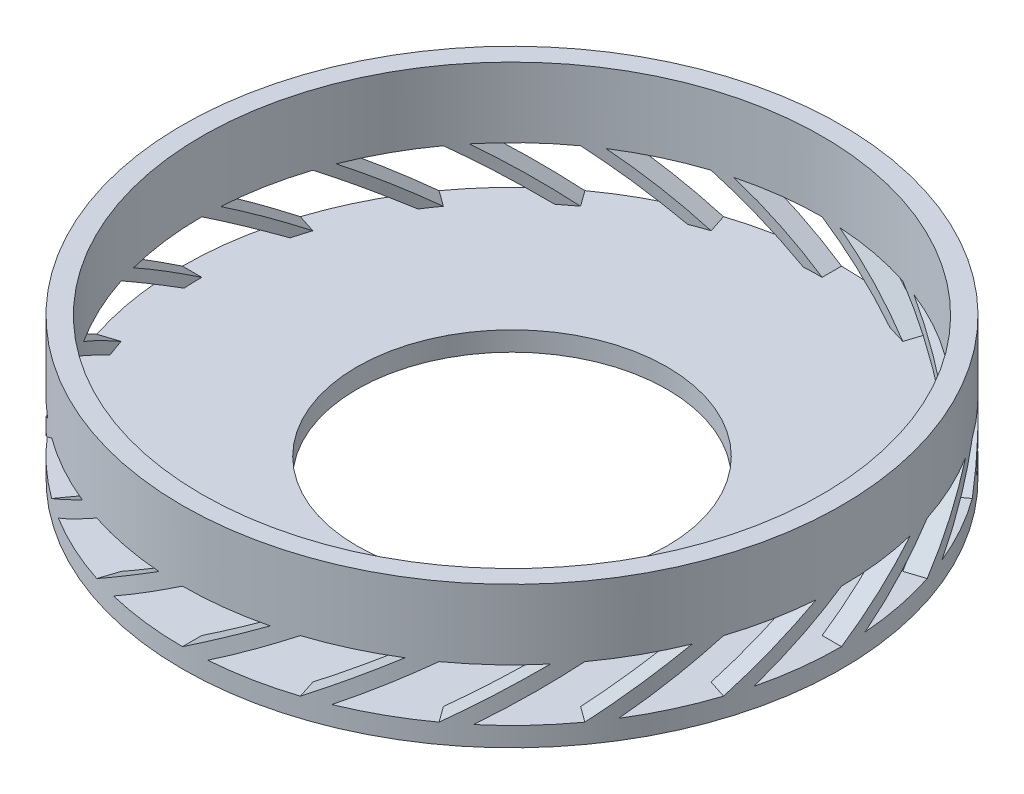
SolidWorks part; units mm, degrees
ref_plane "Front Plane" through (0, 0, 0) normal (0, 0, 1) x (1, 0, 0)
ref_plane "Top Plane" through (0, 0, 0) normal (0, 1, 0) x (1, 0, 0)
ref_plane "Right Plane" through (0, 0, 0) normal (1, 0, 0) x (0, 0, -1)
sketch "Sketch2" plane through (0, 0, 0) normal (0, 1, 0) x (1, 0, 0)
  circle A0 centre (0, 0) radius 26.9875
extrude "Boss-Extrude1" add sketch "Sketch2" along normal blind 11.5951
shell "Shell1" thickness 1.5875 removed face at (0, 11.5951, 26.9875)
ref_axis "Axis1" through (0, 11.5951, 0) along (0, -1, 0)
sketch "Sketch5" plane through (0, 1.5875, 0) normal (0, 1, 0) x (1, 0, 0)
  circle A0 centre (0, 0) radius 12.7
extrude "Cut-Extrude1" cut sketch "Sketch5" against normal through all both and the other way through all
sketch "Sketch6" plane through (0, 0, 0) normal (0, 0, 1) x (1, 0, 0)
  line L0 (0, 1.5875) -> (6.4136, 1.5875)
  line L1 (26.9875, 11.5951) -> (-26.9875, 11.5951) construction
  line L2 (0, 1.5875) -> (-6.4136, 5.8801)
  line L3 (0, 11.5951) -> (0, 8.356)
  line L8 (0, 0) -> (0, 1.5875)
  line L9 (0, 1.5875) -> (6.4136, 1.5875)
  line L13 (0, 1.5875) -> (0, 5.8801)
  line L14 (6.4136, 1.5875) -> (0, 5.8801)
  line L15 (-6.4136, 5.8801) -> (0, 5.8801)
extrude "Cut-Extrude2" cut sketch "Sketch6" against normal blind 38.1 contours L9 | L0 L2 L15 L14 region at (2.1379, 3.0184, 0)
pattern_circular "CirPattern3" count 20 over 360 about axis through (0, 11.5951, 0) along (0, -1, 0) of "Cut-Extrude2"
